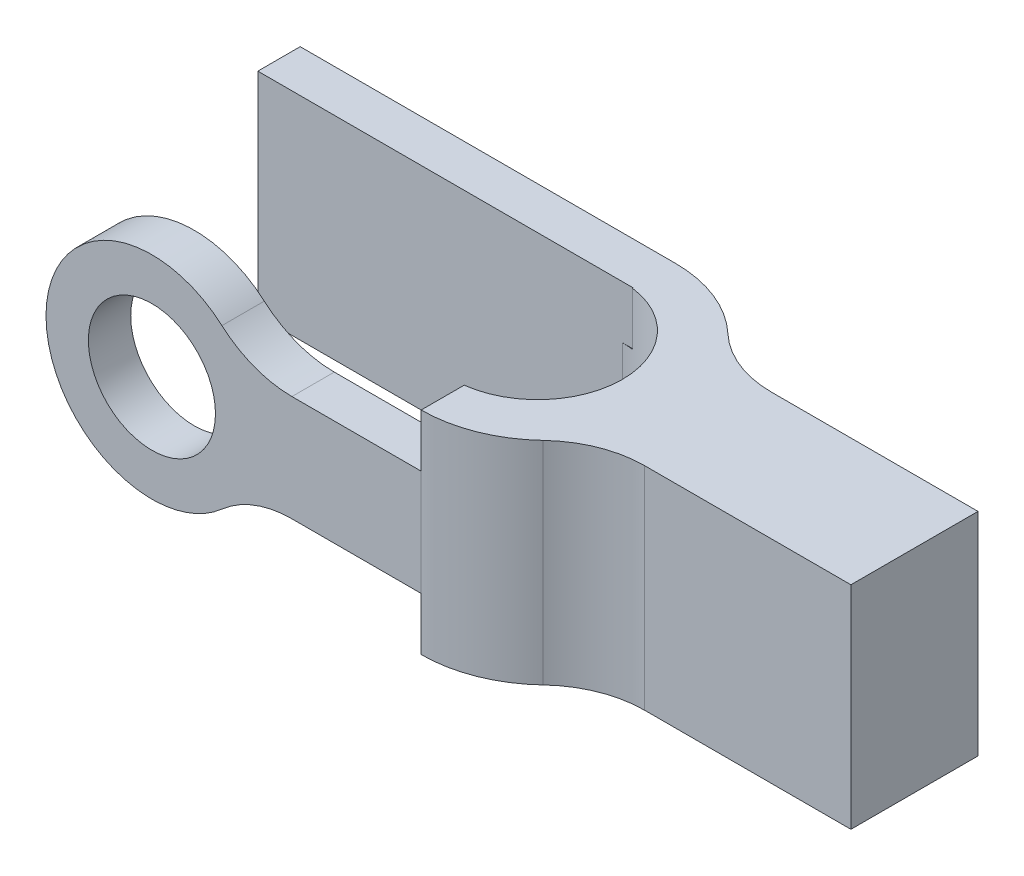
SolidWorks part; units mm, degrees
ref_plane "Front Plane" through (0, 0, 0) normal (0, 0, 1) x (1, 0, 0)
ref_plane "Top Plane" through (0, 0, 0) normal (0, 1, 0) x (1, 0, 0)
ref_plane "Right Plane" through (0, 0, 0) normal (1, 0, 0) x (0, 0, -1)
sketch "Sketch1" plane through (0, 0, 0) normal (0, 1, 0) x (1, 0, 0)
  line L1 (0, 0) -> (-250, 0)
  line L2 (0, 0) -> (0, 120)
  line L3 (0, 120) -> (-250, 120)
  line L4 (-250, 0) -> (-250, 120)
extrude "Boss-Extrude1" add sketch "Sketch1" along normal blind 100
sketch "Sketch2" plane through (0, 100, 0) normal (0, 1, 0) x (1, 0, 0)
  line L0 (-250, 60) -> (0, 60) construction
  line L1 (-250, 120) -> (-250, 0) construction
  line L2 (0, 0) -> (0, 120) construction
  line L3 (0, 30) -> (-97.3878, 30)
  line L4 (0, 90) -> (-97.3878, 90)
  line L5 (0, 0) -> (0, 120)
  line L6 (-250, 0) -> (0, 0) construction
  line L7 (0, 120) -> (-250, 120) construction
  line L8 (-250, 0) -> (0, 0)
  line L9 (-250, 120) -> (-250, 0)
  line L10 (0, 120) -> (-250, 120)
  line L11 (-177.8861, 100) -> (-250, 100)
  line L12 (-177.8861, 20) -> (-250, 20)
  line L17 (0, 0) -> (0, 120)
  line L18 (0, 120) -> (-250, 120)
  line L19 (-250, 120) -> (-250, 0)
  line L20 (-250, 0) -> (0, 0)
  line L21 (0, 0) -> (0, 120)
  line L22 (0, 120) -> (-250, 120)
  line L23 (-250, 120) -> (-250, 0)
  line L24 (-250, 0) -> (0, 0)
  arc A0 (-131.7052, 103.6364) -> (-217.6075, 100) centre (-172.8861, 60) ccw
  arc A1 (-177.8861, 20) -> (-177.8861, 100) centre (-177.8861, 60) ccw
  arc A2 (-97.3878, 30) -> (-131.7052, 16.3636) centre (-97.3878, -20) ccw
  arc A3 (-97.3878, 90) -> (-131.7052, 103.6364) centre (-97.3878, 140) cw
  arc A4 (-217.6075, 20) -> (-131.7052, 16.3636) centre (-172.8861, 60) ccw
  point P19 (-120.9246, 30)
  point P22 (-120.9246, 90)
  line M26 (0, 0) -> (0, 120)
  line M27 (0, 120) -> (-250, 120)
  dimension "D2" = 5
  dimension "D3" = 80
  dimension "D4" = 50
  dimension "D1" = 30
  dimension "D5" = 0
extrude "Cut-Extrude1" cut sketch "Sketch2" against normal blind 100 contours L0 L23 L12 A1 | L9 L0 A1 L11 | A4 L24 L3 A2 M26 | A3 L4 A0 M26 M27 region at (-197.8501, 100, -79.0825) region at (-197.8501, 100, -40.9175) region at (-67.7366, 100, -14.0612) region at (-67.7366, 100, -105.9388)
sketch "Sketch3" plane through (0, 0, 0) normal (0, 0, 1) x (1, 0, 0)
  line L0 (-250, 50) -> (0, 50) construction
  line L1 (-250, 100) -> (-250, 0) construction
  line L2 (0, 0) -> (0, 100) construction
sketch "Sketch5" plane through (-250, 0, 0) normal (-1, 0, 0) x (0, 0, 1)
  line L1 (-120, 100) -> (-100, 100)
  line L2 (-120, 100) -> (-120, 0)
  line L3 (-120, 0) -> (-100, 0)
  line L4 (-100, 100) -> (-100, 0)
extrude "Boss-Extrude2" add sketch "Sketch5" along normal blind 100
sketch "Sketch6" plane through (-250, 0, 0) normal (-1, 0, 0) x (0, 0, 1)
  line L1 (-20, 100) -> (0, 100)
  line L2 (-20, 100) -> (-20, 0)
  line L3 (-20, 0) -> (0, 0)
  line L4 (0, 100) -> (0, 0)
extrude "Boss-Extrude3" add sketch "Sketch6" along normal blind 100
sketch "Sketch7" plane through (0, 0, 0) normal (0, 0, 1) x (1, 0, 0)
  line L0 (-250, 50) -> (-350, 50) construction
  line L1 (-350, 0) -> (-350, 100) construction
  line L2 (0, 75) -> (-233.8956, 75)
  line L3 (0, 0) -> (0, 100) construction
  line L4 (-250, 50) -> (0, 50) construction
  line L5 (0, 25) -> (-233.8168, 25)
  arc A0 (-266.9478, 87.4826) -> (-266.9084, 12.4826) centre (-300, 49.9652) ccw
  circle A1 centre (-300, 49.9652) radius 30
  arc A2 (-233.8956, 75) -> (-266.9478, 87.4826) centre (-233.8956, 125) cw
  arc A3 (-233.8168, 25) -> (-266.9084, 12.4826) centre (-233.8168, -25) ccw
  point P18 (-256.7188, 75)
  line M3 (-350, 0) -> (-172.8861, 0)
  line M4 (-172.8861, 0) -> (-172.8861, 100)
  line M5 (-172.8861, 100) -> (-350, 100)
  line M6 (-350, 100) -> (-350, 0)
  dimension "D1" = 25
  dimension "D2" = 50
  dimension "D3" = 50
extrude "Cut-Extrude2" cut sketch "Sketch7" against normal blind 100 contours L0 A1 | A1 L0 | A2 L2 A0 M4 M5 M6 | A0 M6 M3 | L5 A3 A0 M3 M4 region at (-300, 37.2516, 0) region at (-338.8735, 11.169, 0) region at (-242.7962, 88.5466, 0) region at (-300, 62.7164, 0) region at (-220.7608, 11.523, 0)
